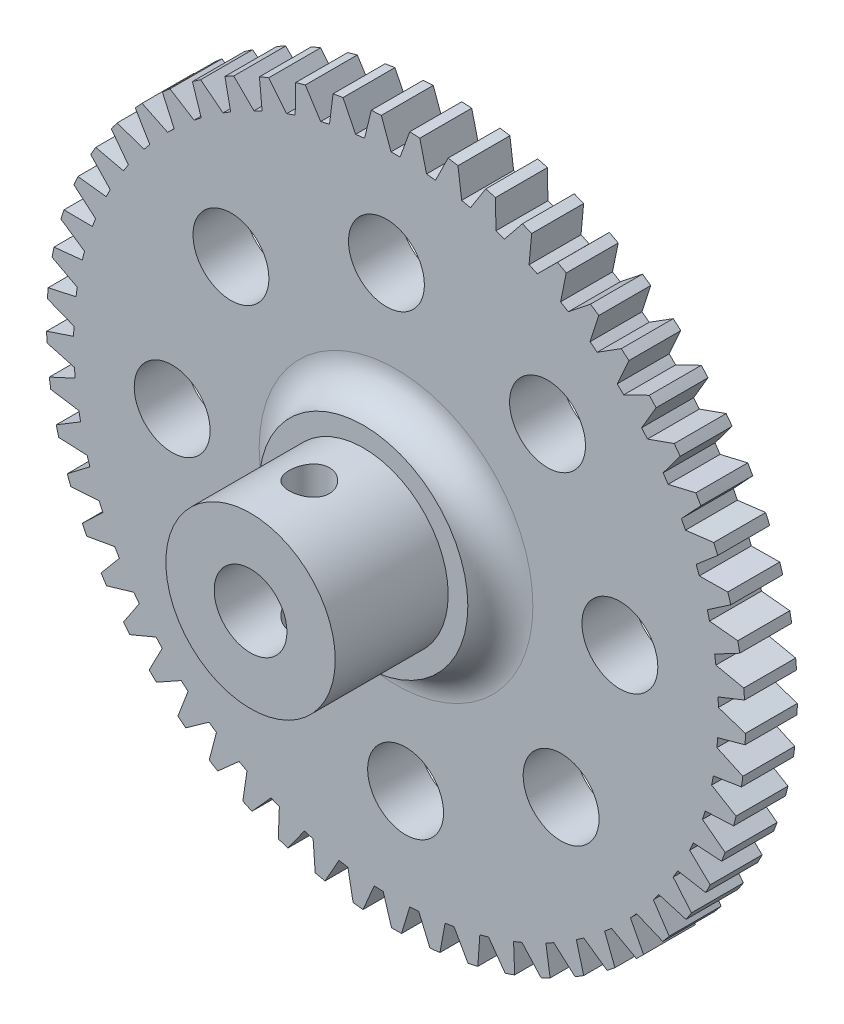
SolidWorks part; units mm, degrees
ref_plane "Front Plane" through (0, 0, 0) normal (0, 0, 1) x (1, 0, 0)
ref_plane "Top Plane" through (0, 0, 0) normal (0, 1, 0) x (1, 0, 0)
ref_plane "Right Plane" through (0, 0, 0) normal (1, 0, 0) x (0, 0, -1)
sketch "Sketch1" plane through (0, 0, 0) normal (0, 0, 1) x (1, 0, 0)
  circle A0 centre (0, 0) radius 19.645
  dimension "D1" = 39.29
extrude "Extrude1" add sketch "Sketch1" along normal blind 2.921
sketch "Sketch3" plane through (0, 0, 0) normal (0, 0, -1) x (-1, 0, 0)
  line L0 (0, 0) -> (0, -19.645) construction
  line L1 (0, 0) -> (2.1046, -19.5319) construction
  line L2 (0.7186, -18.1121) -> (0.254, -19.6434)
  line L3 (1.2259, -18.0848) -> (1.8519, -19.5575)
  line L4 (0, 0) -> (1.0538, -19.6167) construction
  line L5 (0, -19.645) -> (0.254, -19.6434) construction
  line L6 (1.8519, -19.5575) -> (2.1046, -19.5319) construction
  circle A0 centre (0, 0) radius 19.645 construction
  arc A1 (0.254, -19.6434) -> (1.8519, -19.5575) centre (0, 0) ccw
  arc A2 (0.7186, -18.1121) -> (1.2259, -18.0848) centre (0, 0) ccw
  dimension "D1" = 0.254
  dimension "D3" = 1.6002
  dimension "D4" = 1.6002
  dimension "D5" = 0.508
extrude "Cut-Extrude1" cut sketch "Sketch3" against normal through all
ref_axis "Axis1" through (0, 0, -18.3363) along (0, 0, 1)
pattern_circular "CirPattern1" count 57 over 360 about axis through (0, 0, -18.3363) along (0, 0, 1) of "Cut-Extrude1"
sketch "Sketch4" plane through (0, 0, 0) normal (0, 0, -1) x (-1, 0, 0)
  circle A0 centre (0, 0) radius 5.8674
  dimension "D1" = 11.7348
extrude "Extrude2" add sketch "Sketch4" along normal blind 1.8288
fillet "Fillet1" radius 1.8288 1 edges at (5.8674, 0, 0)
ref_plane "Plane1" through (0, 0, 1.4605) normal (0, 0, -1) x (-1, 0, 0)
sketch "Sketch5" plane through (0, 0, -1.8288) normal (0, 0, -1) x (-1, 0, 0)
  circle A0 centre (0, 0) radius 3.9116
  dimension "D1" = 7.8232
mirror "Mirror3" about plane through (0, 0, 1.4605) normal (0, 0, -1) of "Extrude2"
fillet "Fillet2" radius 1.8288 1 edges at (5.8674, 0, 2.921)
extrude "Cut-Extrude3" cut sketch "Sketch5" against normal through all
sketch "Sketch7" plane through (0, 0, 2.921) normal (0, 0, 1) x (1, 0, 0)
  line L0 (0, 0) -> (-14.4725, 13.2843) construction
  circle A0 centre (-9.2813, 8.5192) radius 2.1336
  arc A1 (-14.2801, 13.491) -> (-14.662, 13.0748) centre (0, 0) ccw construction
  point P8 (-14.4725, 13.2843)
  dimension "D1" = 4.2672
  dimension "D3" = 12.5984
extrude "Cut-Extrude4" cut sketch "Sketch7" against normal up to surface (2.921 mm away) up to face at (7.6962, 0, 0)
pattern_circular "CirPattern2" count 8 every 45 about axis through (0, 0, -1.8288) along (0, 0, -1) of "Cut-Extrude4"
sketch "Sketch8" plane through (0, 0, 4.7498) normal (0, 0, 1) x (1, 0, 0)
  circle A0 centre (0, 0) radius 2.045
  circle A1 centre (0, 0) radius 4.7625
  dimension "D1" = 9.525
  dimension "D2" = 4.09
extrude "Boss-Extrude1" add sketch "Sketch8" along normal blind 6.35 and the other way up to surface (6.5786 mm away) other way up to face at (-3.9116, 0, -1.8288)
hole_wizard "#4-40 Tapped Hole1" positions "3DSketch1" profile "Sketch11" tap size "#4-40" standard "Ansi Inch" end condition through all
sketch3d "3DSketch1"
  point P0 (0, 4.7625, 7.7978)
  dimension "D1" = 3.302
sketch "Sketch11" plane through (0, 4.7625, 7.7978) normal (1, 0, 0) x (0, 0, 1)
  line L0 (0, 0) -> (0, 24.4075)
  line L1 (0, 24.4075) -> (1.1303, 24.4075)
  line L2 (1.1303, 24.4075) -> (1.1303, 0)
  line L5 (1.1303, 0) -> (0, 0)
  line L11 (0, -6.35) -> (0, 107.95) construction
  dimension "Thread Major Dia." = 2.2606
  dimension "Thru Tap Drill Depth" = 24.4075
